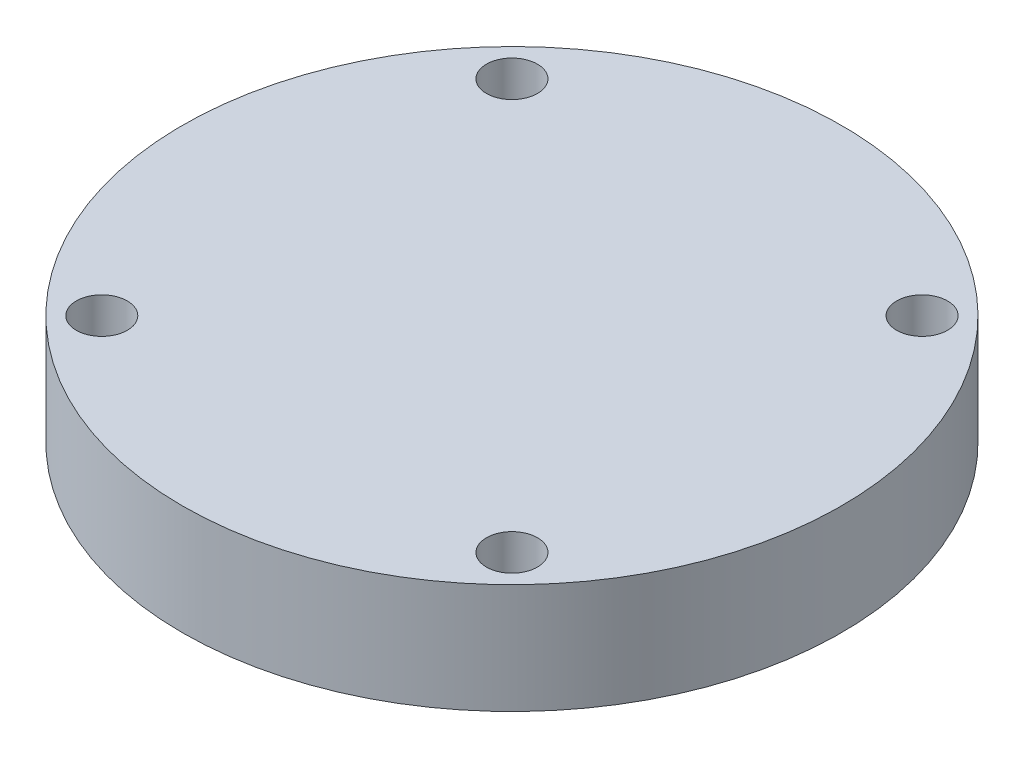
SolidWorks part; units mm, degrees
material "Copper"
ref_plane "Front Plane" through (0, 0, 0) normal (0, 0, 1) x (1, 0, 0)
ref_plane "Top Plane" through (0, 0, 0) normal (0, 1, 0) x (1, 0, 0)
ref_plane "Right Plane" through (0, 0, 0) normal (1, 0, 0) x (0, 0, -1)
ref_axis "Y Axis" through (0, 6.6675, 0) along (0, -1, 0)
sketch "outer" plane through (0, 0, 0) normal (0, 1, 0) x (1, 0, 0)
  circle A0 centre (0, 0) radius 19.05
  dimension "D1" = 38.1
extrude "Body" add sketch "outer" along normal blind 6.35
sketch "inner" plane through (0, 0, 0) normal (0, 1, 0) x (1, 0, 0)
  circle A0 centre (0, 0) radius 11.938
  dimension "D1" = 23.876
extrude "Pocket" cut sketch "inner" along normal blind 3.81
sketch "Screw Position" plane through (0, 0, 0) normal (0, 1, 0) x (1, 0, 0)
  point P0 (-11.8539, 11.8539)
  dimension "D1" = 16.764
hole_wizard "#4 Clearance Hole1" positions "Sketch7" profile "Sketch8" hole size "#4" standard "ANSI Inch" end condition through all
sketch "Sketch7" plane through (0, 6.35, 0) normal (0, 1, 0) x (1, 0, 0)
  point P0 (-11.8539, 11.8539)
sketch "Sketch8" plane through (-11.8539, 6.35, -11.8539) normal (1, 0, 0) x (0, 0, 1)
  line L0 (0, 0) -> (0, 6.35)
  line L1 (0, 6.35) -> (1.4732, 6.35)
  line L2 (1.4732, 6.35) -> (1.4732, 0)
  line L5 (1.4732, 0) -> (0, 0)
  line L11 (0, -6.35) -> (0, 107.95) construction
  dimension "Thru Hole Dia." = 2.9464
  dimension "Thru Hole Depth" = 6.35
pattern_circular "Screw Holes" count 4 over 360 about axis through (0, 6.6675, 0) along (0, -1, 0) of "#4 Clearance Hole1"
sketch "Post Sketch" plane through (0, 0, 0) normal (0, 1, 0) x (1, 0, 0)
  circle A0 centre (0, -7) radius 1.2065
  circle A1 centre (5.3033, -5.3033) radius 1.2065
  point P0 (0, -7)
  point P1 (5.3033, -5.3033)
  dimension "D3" = 2.413
  dimension "D4" = 2.413
  dimension "D1" = 7
  dimension "D2" = 7.5
extrude "Post" add sketch "Post Sketch" against normal blind 4.572 from surface starting at face at (0, 3.81, 11.938)
pattern_circular "CirPattern1" count 4 over 360 about axis through (0, 6.6675, 0) along (0, -1, 0) of "Post"
equation "\"outer_d\"= 3 / 2in"
equation "\"top_h\"= 1 / 4in"
equation "\"screw_r\"= 0.66in"
equation "\"inner_d\"= 0.94in"
equation "\"inner_h\"= 150mil"
equation "\"D1@outer\" = \"outer_d\""
equation "\"D1@Body\" = \"top_h\""
equation "\"D1@inner\"=\"inner_d\""
equation "\"D1@Pocket\" = \"inner_h\""
equation "\"D1@Screw Position\"=\"screw_r\""
equation "\"post_r1\"= 7mm"
equation "\"post_r2\"= 7.5mm"
equation "\"post_bottom_h\"= 0.03in"
equation "\"D1@Post Sketch\" = \"post_r1\""
equation "\"D2@Post Sketch\" = \"post_r2\""
equation "\"post_d\"= 0.095in"
equation "\"D3@Post Sketch\"=\"post_d\""
equation "\"D4@Post Sketch\"=\"post_d\""
equation "\"D1@Post\" = \"inner_h\" + \"post_bottom_h\""
